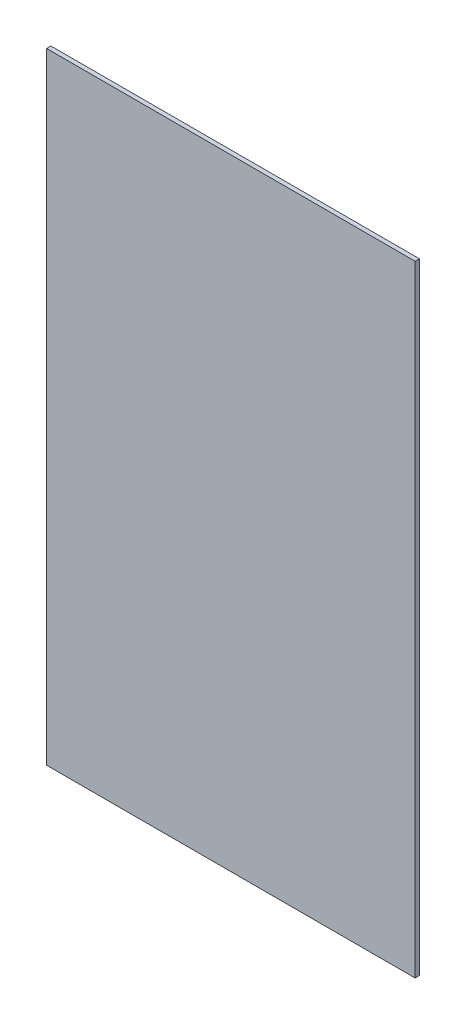
SolidWorks part; units mm, degrees
ref_plane "Спереди" through (0, 0, 0) normal (0, 0, 1) x (1, 0, 0)
ref_plane "Сверху" through (0, 0, 0) normal (0, 1, 0) x (1, 0, 0)
ref_plane "Справа" through (0, 0, 0) normal (1, 0, 0) x (0, 0, -1)
other "Configuration Table"
sketch "Эскиз1" plane through (0, 0, 0) normal (0, 0, 1) x (1, 0, 0)
  line L1 (0, -436.3) -> (-518, -436.3)
  line L2 (0, -436.3) -> (0, 436.3)
  line L3 (0, 436.3) -> (-518, 436.3)
  line L4 (-518, -436.3) -> (-518, 436.3)
extrude "Бобышка-Вытянуть1" add sketch "Эскиз1" against normal blind 6
equation "\"Ширина груза\"= 420"
equation "\"Глубина груза\"= 490"
equation "\"Высота груза\"= 297"
equation "\"Ширина ячейки\"= \"Ширина груза\" + 10"
equation "\"Глубина ячейки\"= \"Глубина груза\" + 10"
equation "\"Высота ячейки\"= \"Высота груза\" + 10 + 13"
equation "\"Колво ячеек ширина\"= 2"
equation "\"Колво ячеек высота\"= 2"
equation "\"Толщина стенки\" = 6"
equation "\"Крепление дверцы\"= 5"
equation "\"Ширина рейки\"= \"Толщина шестерни\""
equation "\"Высота рейки\"= 20"
equation "\"Высота пола\"= 20"
equation "\"Колво полозьев\"= 5"
equation "\"Отступ рейки\"= 20"
equation "\"Глубина каретки\"= \"Глубина ячейки\" + 30 + \"Мотор Y высота корпуса\" + 20"
equation "\"Длинна рейки\"= ( \"Ширина ячейки\" + \"Толщина стенки\" + \"Крепление дверцы\" ) * \"Колво ячеек ширина\" + \"Ширина ячейки выгрузки\" * \"Колво выгрузки\" + \"Толщина стенки\""
equation "\"Отступ шпильки\"= 26"
equation "\"Диаметр шпильки\"= 5"
equation "\"Длинна шпильки\"= ( \"Высота ячейки\" + \"Толщина стенки\" + \"Высота пола\" ) * \"Колво ячеек высота\" + ( \"Толщина стенки\" + \"Отступ рейки\" ) * 2 "
equation "\"Ширина пластины\"= 50  "
equation "\"Высота зона выгрузки\"= \"Высота ячейки\" * 2 + \"Толщина стенки\" * 2"
equation "\"Колво выгрузки\"= 1"
equation "\"Ширина ячейки выгрузки\"= \"Ширина ячейки\" + \"Толщина стенки\" + \"Отступ крепления мотора фиксации\"*2"
equation "\"Отступ крепления мотора фиксации\" = 30"
equation "\"Мотор X ширина корпуса\"= 42.3"
equation "\"Мотор X высота корпуса\"= 42.3"
equation "\"Мотор X длина корпуса\"= 40"
equation "\"Мотор X вылет вала\"= 19.8"
equation "\"Мотор Y ширина корпуса\"= 42.3"
equation "\"Мотор Y высота корпуса\"= 42.3"
equation "\"Мотор Y длина корпуса\"= 48"
equation "\"Мотор Y вылет вала\"= 30"
equation "\"Мотор Z ширина корпуса\"= 42"
equation "\"Мотор Z высота корпуса\"= 42"
equation "\"Мотор Z длина корпуса\"= 40"
equation "\"Мотор Z вылет вала\"= 23"
equation "\"Мотор диаметр вала ПРЕДВ\"= 5"
equation "\"Мотор шаг крепления ПРЕДВ\"= 31"
equation "\"Мотор диаметр отверстий ПРЕДВ\"= 3"
equation "\"Мотор глубина отверстий ПРЕДВ\"= 4.5"
equation "\"Мотор диаметр буртика ПРЕДВ\"= 22"
equation "\"Мотор высота буртика ПРЕДВ\"= 2"
equation "\"Мотор диаметр шкива ПРЕДВ\"= 16"
equation "\"Мотор длина шкива ПРЕДВ\"= 12"
equation "\"Мотор отступ шкива ПРЕДВ\"= 5"
equation "\"Мотор X шаг градусов\"= 1.8"
equation "\"Мотор Y шаг градусов\"= 1.8"
equation "\"Мотор Z шаг градусов\"= 1.8"
equation "\"Мотор Y диаметр ротора\"= 25.78"
equation "\"Толщина шестерни\"= 10"
equation "\"D1@Бобышка-Вытянуть1\"=\"Толщина стенки\""
